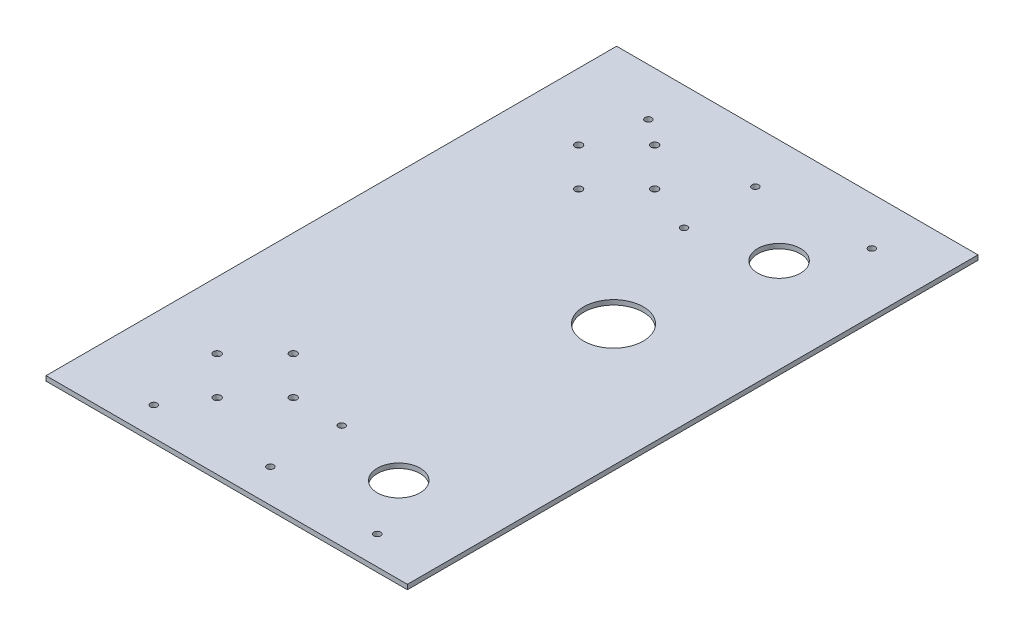
SolidWorks part; units mm, degrees
material "6061-T6 (SS)"
ref_plane "Front Plane" through (0, 0, 0) normal (0, 0, 1) x (1, 0, 0)
ref_plane "Top Plane" through (0, 0, 0) normal (0, 1, 0) x (1, 0, 0)
ref_plane "Right Plane" through (0, 0, 0) normal (1, 0, 0) x (0, 0, -1)
sketch "Sketch1" plane through (0, 0, 0) normal (0, 1, 0) x (1, 0, 0)
  line L1 (120.65, -190.5) -> (-120.65, -190.5)
  line L2 (120.65, -190.5) -> (120.65, 190.5)
  line L3 (120.65, 190.5) -> (-120.65, 190.5)
  line L4 (-120.65, -190.5) -> (-120.65, 190.5)
  line L5 (120.65, -190.5) -> (-120.65, 190.5) construction
  line L6 (120.65, 190.5) -> (-120.65, -190.5) construction
  point P0 (0, 0)
  dimension "D1" = 241.3
  dimension "D2" = 381
extrude "Boss-Extrude1" add sketch "Sketch1" along normal blind 3.175
sketch "Sketch6" plane through (0, 3.175, 0) normal (0, 1, 0) x (1, 0, 0)
  line L0 (120.65, 190.5) -> (-120.65, 190.5) construction
  line L1 (57.7084, -133.35) -> (-43.8916, -133.35) construction
  line L2 (57.7084, 120.65) -> (-43.8916, 120.65) construction
  line L3 (57.7084, 120.65) -> (120.65, 120.65) construction
  line L4 (120.65, -190.5) -> (120.65, 190.5) construction
  line L5 (-120.65, 190.5) -> (-120.65, -190.5) construction
  circle A0 centre (-43.8916, -133.35) radius 38.1 construction
  circle A1 centre (-43.8916, 120.65) radius 38.1 construction
  circle A2 centre (57.7084, -133.35) radius 38.1 construction
  circle A3 centre (57.7084, 120.65) radius 38.1 construction
  point P5 (31.3429, 123.1524)
  dimension "D1" = 76.2
  dimension "D5" = 177.8
  dimension "D2" = 254
  dimension "D3" = 101.6
  dimension "D4" = 76.7584
  dimension "D6" = 69.85
hole_wizard "#10 (0.1935) Diameter Hole1" positions "Sketch4" profile "Sketch5" hole size "#10" standard "ANSI Inch" end condition through all
sketch "Sketch4" plane through (0, 3.175, 0) normal (0, 1, 0) x (1, 0, 0)
  arc A0 (-48.7807, -95.25) -> (-52.8193, -95.25) centre (-50.8, -95.25) ccw construction
  arc A1 (-52.8193, -95.25) -> (-48.7807, -95.25) centre (-50.8, -95.25) ccw construction
  arc A2 (-74.1807, -120.65) -> (-78.2193, -120.65) centre (-76.2, -120.65) ccw construction
  arc A3 (-78.2193, -120.65) -> (-74.1807, -120.65) centre (-76.2, -120.65) ccw construction
  arc A4 (-48.7807, -146.05) -> (-52.8193, -146.05) centre (-50.8, -146.05) ccw construction
  arc A5 (-52.8193, -146.05) -> (-48.7807, -146.05) centre (-50.8, -146.05) ccw construction
  arc A6 (-23.3807, -120.65) -> (-27.4193, -120.65) centre (-25.4, -120.65) ccw construction
  arc A7 (-27.4193, -120.65) -> (-23.3807, -120.65) centre (-25.4, -120.65) ccw construction
  arc A8 (-48.7807, -95.25) -> (-52.8193, -95.25) centre (-50.8, -95.25) ccw construction
  arc A9 (-52.8193, -95.25) -> (-48.7807, -95.25) centre (-50.8, -95.25) ccw construction
  arc A10 (-74.1807, -120.65) -> (-78.2193, -120.65) centre (-76.2, -120.65) ccw construction
  arc A11 (-78.2193, -120.65) -> (-74.1807, -120.65) centre (-76.2, -120.65) ccw construction
  arc A12 (-48.7807, -146.05) -> (-52.8193, -146.05) centre (-50.8, -146.05) ccw construction
  arc A13 (-52.8193, -146.05) -> (-48.7807, -146.05) centre (-50.8, -146.05) ccw construction
  arc A14 (-23.3807, -120.65) -> (-27.4193, -120.65) centre (-25.4, -120.65) ccw construction
  arc A15 (-27.4193, -120.65) -> (-23.3807, -120.65) centre (-25.4, -120.65) ccw construction
  arc A16 (-23.3807, 120.65) -> (-27.4193, 120.65) centre (-25.4, 120.65) ccw construction
  arc A17 (-27.4193, 120.65) -> (-23.3807, 120.65) centre (-25.4, 120.65) ccw construction
  arc A18 (-48.7807, 146.05) -> (-52.8193, 146.05) centre (-50.8, 146.05) ccw construction
  arc A19 (-52.8193, 146.05) -> (-48.7807, 146.05) centre (-50.8, 146.05) ccw construction
  arc A20 (-74.1807, 120.65) -> (-78.2193, 120.65) centre (-76.2, 120.65) ccw construction
  arc A21 (-78.2193, 120.65) -> (-74.1807, 120.65) centre (-76.2, 120.65) ccw construction
  arc A22 (-48.7807, 95.25) -> (-52.8193, 95.25) centre (-50.8, 95.25) ccw construction
  arc A23 (-52.8193, 95.25) -> (-48.7807, 95.25) centre (-50.8, 95.25) ccw construction
  arc A24 (-23.3807, 120.65) -> (-27.4193, 120.65) centre (-25.4, 120.65) ccw
  arc A25 (-27.4193, 120.65) -> (-23.3807, 120.65) centre (-25.4, 120.65) ccw
  arc A26 (-48.7807, 146.05) -> (-52.8193, 146.05) centre (-50.8, 146.05) ccw
  arc A27 (-52.8193, 146.05) -> (-48.7807, 146.05) centre (-50.8, 146.05) ccw
  arc A28 (-74.1807, 120.65) -> (-78.2193, 120.65) centre (-76.2, 120.65) ccw
  arc A29 (-78.2193, 120.65) -> (-74.1807, 120.65) centre (-76.2, 120.65) ccw
  arc A30 (-48.7807, 95.25) -> (-52.8193, 95.25) centre (-50.8, 95.25) ccw
  arc A31 (-52.8193, 95.25) -> (-48.7807, 95.25) centre (-50.8, 95.25) ccw
  point P0 (-50.8, -146.05)
  point P2 (-76.2, -120.65)
  point P4 (-50.8, -95.25)
  point P6 (-25.4, -120.65)
  point P44 (-50.8, 146.05)
  point P50 (-76.2, 120.65)
  point P56 (-50.8, 95.25)
  point P68 (-25.4, 120.65)
sketch "Sketch5" plane through (-50.8, 3.175, 146.05) normal (1, 0, 0) x (0, 0, 1)
  line L0 (0, 0) -> (0, 3.175)
  line L1 (0, 3.175) -> (2.4574, 3.175)
  line L2 (2.4574, 3.175) -> (2.4574, 0)
  line L5 (2.4574, 0) -> (0, 0)
  line L11 (0, -6.35) -> (0, 107.95) construction
  dimension "Thru Hole Dia." = 4.9149
  dimension "Thru Hole Depth" = 3.175
sketch "Sketch7" plane through (0, 3.175, 0) normal (0, 1, 0) x (1, 0, 0)
  circle A0 centre (57.7084, -133.35) radius 14.2875
  circle A1 centre (57.7084, 120.65) radius 14.2875
  dimension "D1" = 28.575
extrude "Cut-Extrude3" cut sketch "Sketch7" against normal through all
sketch "Sketch10" plane through (0, 3.175, 0) normal (0, 1, 0) x (1, 0, 0)
  circle A0 centre (6.9084, -120.65) radius 2.2479 construction
  circle A1 centre (-67.7041, -171.45) radius 2.2479 construction
  circle A3 centre (6.9084, -168.275) radius 2.2479 construction
  circle A4 centre (81.5209, -171.45) radius 2.2479 construction
  circle A5 centre (6.9084, -120.65) radius 2.2479
  circle A6 centre (-67.7041, -171.45) radius 2.2479
  circle A8 centre (6.9084, -168.275) radius 2.2479
  circle A9 centre (81.5209, -171.45) radius 2.2479
  circle A10 centre (81.5209, 158.75) radius 2.2479 construction
  circle A11 centre (6.9084, 155.575) radius 2.2479 construction
  circle A13 centre (6.9084, 107.95) radius 2.2479 construction
  circle A14 centre (-67.7041, 158.75) radius 2.2479 construction
  circle A15 centre (81.5209, 158.75) radius 2.2479
  circle A16 centre (6.9084, 155.575) radius 2.2479
  circle A18 centre (6.9084, 107.95) radius 2.2479
  circle A19 centre (-67.7041, 158.75) radius 2.2479
extrude "Cut-Extrude5" cut sketch "Sketch10" against normal through all
sketch "Sketch8" plane through (0, 3.175, 0) normal (0, 1, 0) x (1, 0, 0)
  circle A3 centre (38.8835, 28.8822) radius 19.8684
extrude "Cut-Extrude4" cut sketch "Sketch8" against normal through all
